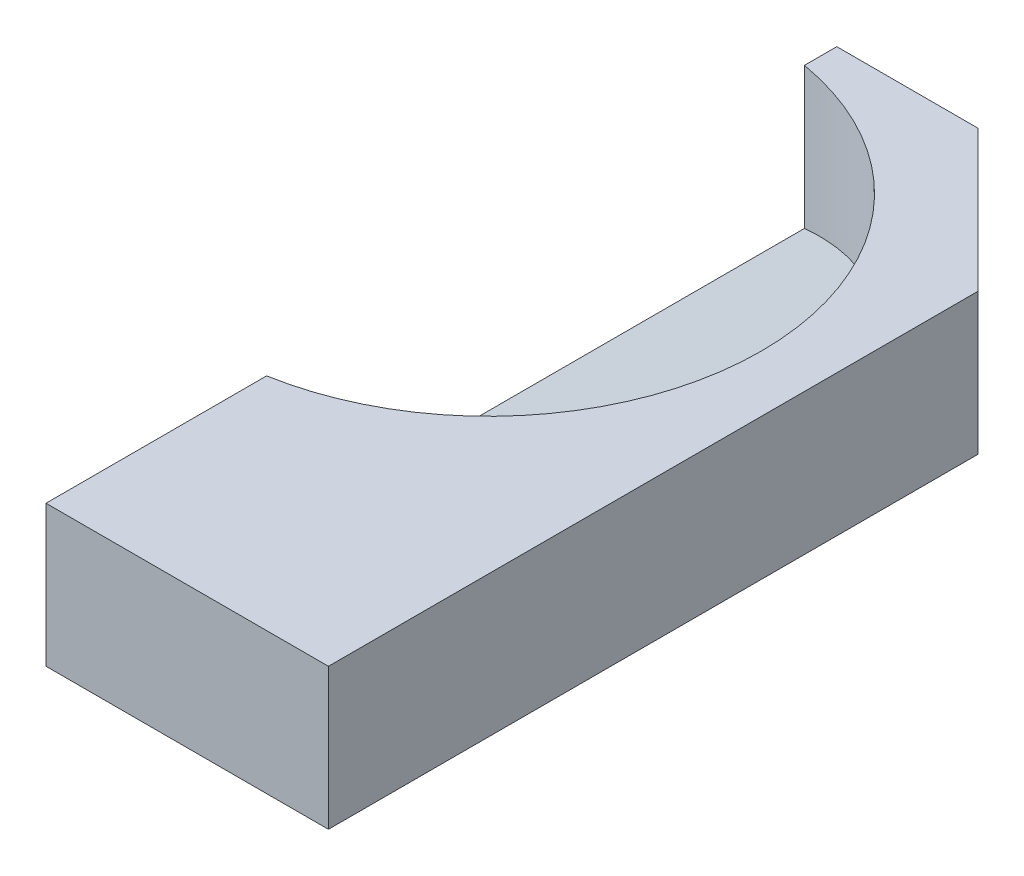
SolidWorks part; units mm, degrees
ref_plane "Plan de face" through (0, 0, 0) normal (0, 0, 1) x (1, 0, 0)
ref_plane "Plan de dessus" through (0, 0, 0) normal (0, 1, 0) x (1, 0, 0)
ref_plane "Plan de droite" through (0, 0, 0) normal (1, 0, 0) x (0, 0, -1)
sketch "Esquisse2" plane through (0, 0, 0) normal (0, 1, 0) x (1, 0, 0)
  line L1 (-32.4129, 40.7804) -> (-2.4129, 40.7804)
  line L2 (-32.4129, 40.7804) -> (-32.4129, -43.2196)
  line L3 (-32.4129, -43.2196) -> (-2.4129, -43.2196)
  line L4 (-2.4129, 40.7804) -> (-2.4129, -43.2196)
  dimension "D1" = 84
  dimension "D2" = 30
extrude "Boss.-Extru.1" add sketch "Esquisse2" along normal blind 15
sketch "Esquisse3" plane through (0, 15, 0) normal (0, 1, 0) x (1, 0, 0)
  line L1 (-32.4129, -43.2196) -> (-2.4129, -43.2196) construction
  line L2 (-32.4129, 40.7804) -> (-32.4129, -43.2196) construction
  circle A0 centre (-37.4129, 8.7804) radius 29
  dimension "D1" = 58
  dimension "D2" = 5
  dimension "D3" = 52
extrude "Enlèv. mat.-Extru.1" cut sketch "Esquisse3" against normal blind 10 contours A0
chamfer "Chanfrein1" distance 5 distance2 20 1 edges at (-32.4129, 5, -8.7804) first distance on face at (-32.4129, 8.75, -3.7804)
chamfer "Chanfrein2" distance 15 angle 45 1 edges at (-2.4129, 7.5, -40.7804)
